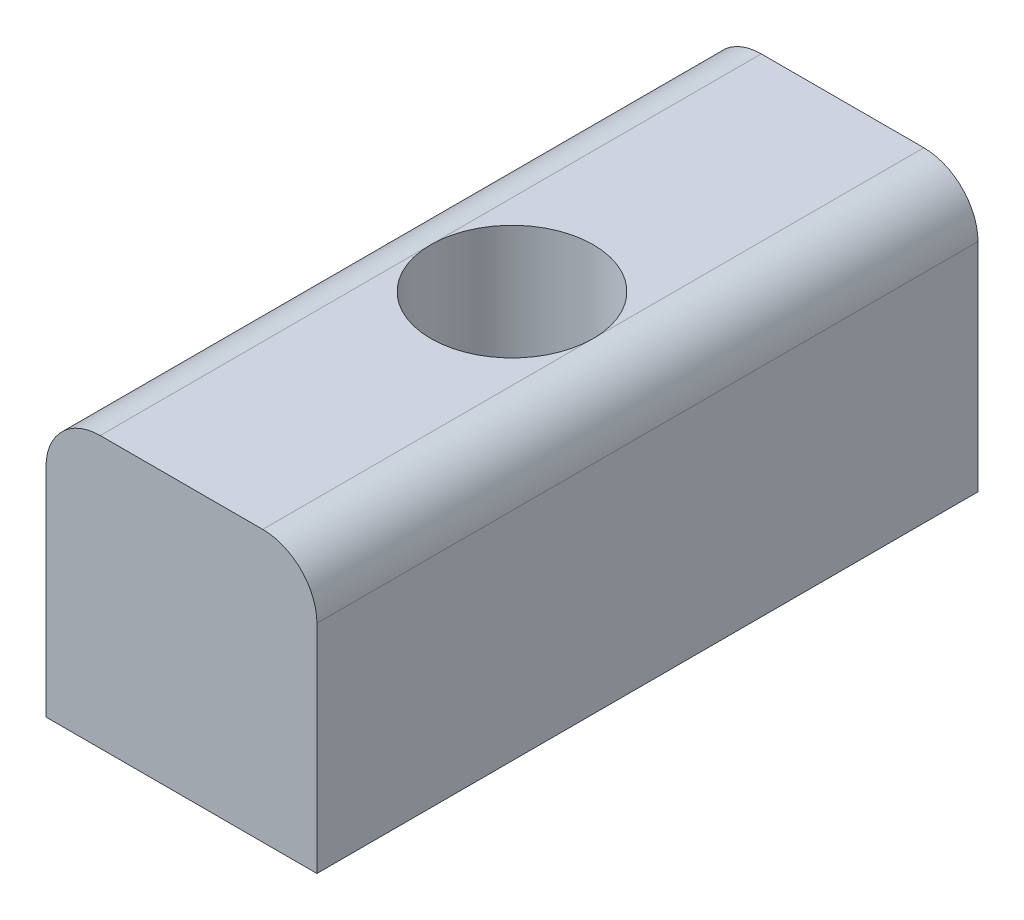
SolidWorks part; units mm, degrees
ref_plane "Front Plane" through (0, 0, 0) normal (0, 0, 1) x (1, 0, 0)
ref_plane "Top Plane" through (0, 0, 0) normal (0, 1, 0) x (1, 0, 0)
ref_plane "Right Plane" through (0, 0, 0) normal (1, 0, 0) x (0, 0, -1)
sketch "Sketch1" plane through (0, 0, 0) normal (0, 1, 0) x (1, 0, 0)
  line L1 (-5, -12.2) -> (5, -12.2)
  line L2 (-5, -12.2) -> (-5, 12.2)
  line L3 (-5, 12.2) -> (5, 12.2)
  line L4 (5, -12.2) -> (5, 12.2)
  line L5 (-5, -12.2) -> (5, 12.2) construction
  line L6 (-5, 12.2) -> (5, -12.2) construction
  circle A0 centre (0, 0) radius 3
  point P0 (0, 0)
  dimension "D2" = 6
  dimension "D1" = 12.2
  dimension "D3" = 10
extrude "Boss-Extrude1" add sketch "Sketch1" along normal blind 10
fillet "Fillet1" radius 2 2 edges at (5, 10, 0) (-5, 10, 0)
